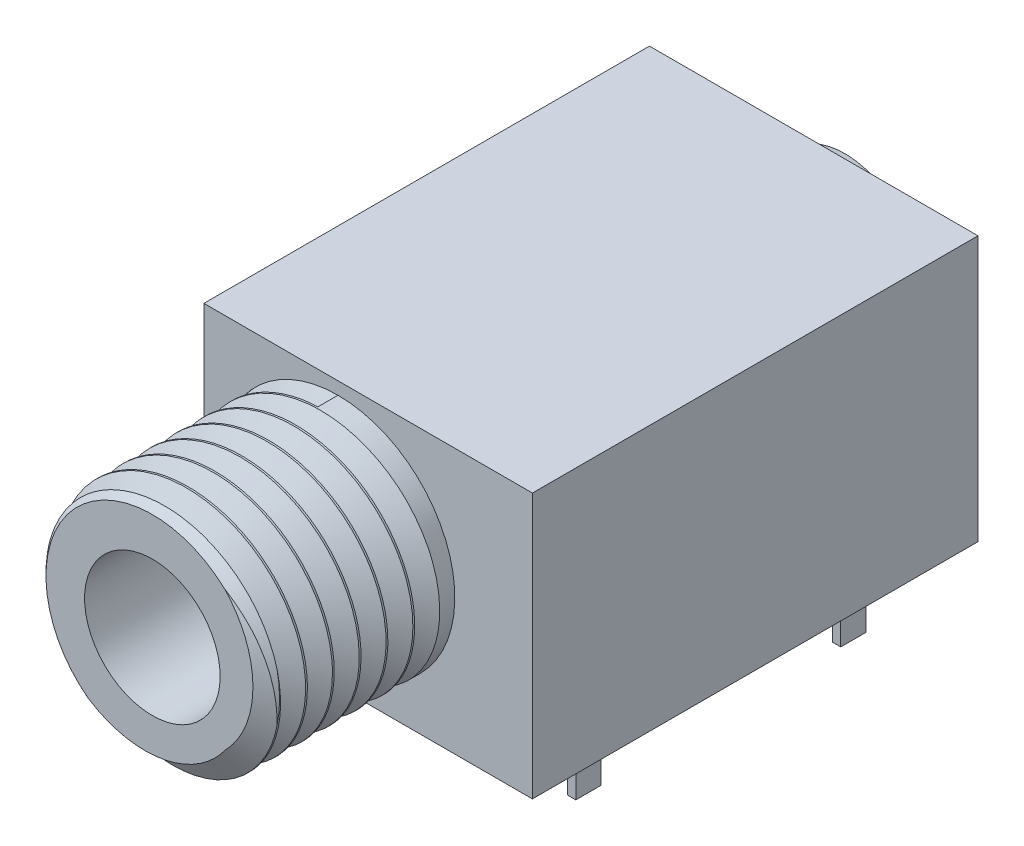
SolidWorks part; units mm, degrees
ref_plane "Front Plane" through (0, 0, 0) normal (0, 0, 1) x (1, 0, 0)
ref_plane "Top Plane" through (0, 0, 0) normal (0, 1, 0) x (1, 0, 0)
ref_plane "Right Plane" through (0, 0, 0) normal (1, 0, 0) x (0, 0, -1)
sketch "Sketch1" plane through (0, 0, 0) normal (0, 1, 0) x (1, 0, 0)
  line L1 (-14.6008, 12.6317) -> (1.1492, 12.6317)
  line L2 (-14.6008, 12.6317) -> (-14.6008, -8.7283)
  line L3 (-14.6008, -8.7283) -> (1.1492, -8.7283)
  line L4 (1.1492, 12.6317) -> (1.1492, -8.7283)
  dimension "D1" = 15.75
  dimension "D2" = 21.36
extrude "Boss-Extrude1" add sketch "Sketch1" along normal blind 12.7
sketch "Sketch3" plane through (0, 0, -12.6317) normal (0, 0, -1) x (-1, 0, 0)
  line L0 (-1.1492, 0) -> (14.6008, 0) construction
  line L1 (14.6008, 12.7) -> (14.6008, 0) construction
  circle A0 centre (8.1708, 6.5) radius 4
  point P6 (9.1995, 6.4563)
  dimension "D1" = 6.5
  dimension "D2" = 6.43
extrude "Boss-Extrude2" add sketch "Sketch3" along normal blind 2.94 draft 10
sketch "Sketch4" plane through (0, 0, 8.7283) normal (0, 0, 1) x (1, 0, 0)
  line L0 (-14.6008, 12.7) -> (-14.6008, 0) construction
  line L1 (-14.6008, 0) -> (1.1492, 0) construction
  circle A0 centre (-8.1708, 6.5) radius 5.6
  dimension "D1" = 6.43
  dimension "D2" = 6.5
extrude "Boss-Extrude3" add sketch "Sketch4" along normal blind 8.9
chamfer "Chamfer1" distance 0.5 angle 45 1 edges at (-2.5708, 6.5, 17.6283)
ref_plane "Plane1" through (0, 6.5, 0) normal (0, -1, 0) x (-1, 0, 0)
sketch "Sketch6" plane through (0, 6.5, 0) normal (0, -1, 0) x (-1, 0, 0)
  line L0 (13.7708, -16.5283) -> (13.7708, -17.7283)
  line L1 (13.7708, -17.1283) -> (13.7708, -8.7283) construction
  line L2 (2.5708, -17.1283) -> (13.7708, -17.1283) construction
  line L3 (13.7708, -17.7283) -> (12.7315, -17.1283)
  line L4 (12.7315, -17.1283) -> (13.7708, -16.5283)
  line L5 (8.1708, -18.6021) -> (8.1708, -10.6988) construction
  point P4 (13.7708, -17.1283)
  dimension "D1" = 5.6
  dimension "D3" = 1.2
sketch "Sketch9" plane through (0, 0, 17.6283) normal (0, 0, 1) x (1, 0, 0)
  circle A0 centre (-8.1708, 6.5) radius 5.6
curve "Helix/Spiral1" pitch 1.2857 height 9 radius 5.6 centre (-8.1708, 6.5, 17.6283) axis (0, 0, -1) start towards (0, 1, 0)
sweep "Cut-Sweep1" cut profiles "Sketch6" path "Helix/Spiral1"
sketch "Sketch13" plane through (0, 0, 17.6283) normal (0, 0, 1) x (1, 0, 0)
  circle A0 centre (-8.1708, 6.5) radius 3.25
  dimension "D1" = 6.5
extrude "Cut-Extrude1" cut sketch "Sketch13" against normal blind 29
sketch "Sketch14" plane through (0, 0, 0) normal (0, -1, 0) x (1, 0, 0)
  line L0 (-6.9358, -12.6317) -> (-6.9358, 8.7283) construction
  line L1 (-12.8508, 4.4783) -> (-12.4508, 4.4783)
  line L2 (-12.8508, 4.4783) -> (-12.8508, 3.2783)
  line L3 (-12.8508, 3.2783) -> (-12.4508, 3.2783)
  line L4 (-12.4508, 4.4783) -> (-12.4508, 3.2783)
  line L5 (-12.4508, -8.2217) -> (-12.4508, -9.4217)
  line L6 (-8.2508, -1.3881) -> (-8.2508, 3.8102) construction
  line L7 (-12.8508, -8.2217) -> (-12.8508, -9.4217)
  line L8 (-12.8508, -9.4217) -> (-12.4508, -9.4217)
  line L9 (-12.8508, -8.2217) -> (-12.4508, -8.2217)
  line L10 (-1.0208, -9.4217) -> (-1.4208, -9.4217)
  line L11 (-1.0208, 3.2783) -> (-1.4208, 3.2783)
  line L12 (-1.0208, 4.4783) -> (-1.0208, 3.2783)
  line L13 (-1.4208, 4.4783) -> (-1.4208, 3.2783)
  line L14 (-1.0208, 4.4783) -> (-1.4208, 4.4783)
  line L15 (-1.0208, -8.2217) -> (-1.0208, -9.4217)
  line L16 (-1.0208, -8.2217) -> (-1.4208, -8.2217)
  line L17 (-14.6008, -12.6317) -> (-14.6008, 8.7283) construction
  line L18 (-14.6008, 8.7283) -> (1.1492, 8.7283) construction
  line L19 (-1.4208, -8.2217) -> (-1.4208, -9.4217)
  dimension "D1" = 1.2
  dimension "D2" = 0.4
  dimension "D3" = 2
  dimension "D4" = 5.515
  dimension "D5" = 6.35
  dimension "D6" = 4.2
  dimension "D7" = 4.25
extrude "Boss-Extrude4" add sketch "Sketch14" along normal blind 3.25
